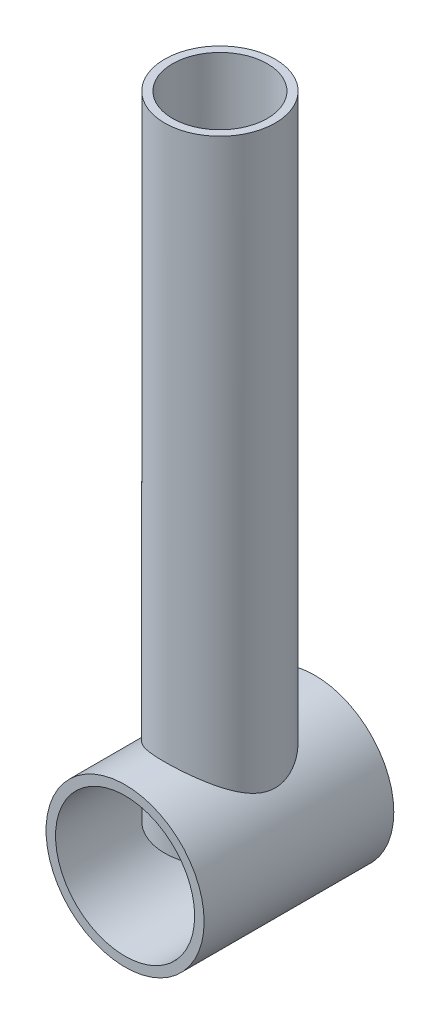
SolidWorks part; units mm, degrees
ref_plane "Ön Düzlem" through (0, 0, 0) normal (0, 0, 1) x (1, 0, 0)
ref_plane "Üst Düzlem" through (0, 0, 0) normal (0, 1, 0) x (1, 0, 0)
ref_plane "Sağ Düzlem" through (0, 0, 0) normal (1, 0, 0) x (0, 0, -1)
sketch "Çizim1" plane through (0, 0, 0) normal (0, 1, 0) x (1, 0, 0)
  circle A0 centre (0, 0) radius 17.5
  circle A1 centre (0, 0) radius 15
  dimension "D1" = 35
  dimension "D2" = 2.5
extrude "Yükseklik-Ekstrüzyon1" add sketch "Çizim1" along normal blind 200
ref_plane "Düzlem1" through (0, 0, 0) normal (0, 0, 1) x (1, 0, 0)
sketch "Çizim2" plane through (0, 0, 0) normal (0, 0, 1) x (1, 0, 0)
  line L0 (-17.5, 0) -> (17.5, 0) construction
  circle A0 centre (0, 0) radius 25
  circle A1 centre (0, 0) radius 22
extrude "Yükseklik-Ekstrüzyon2" add sketch "Çizim2" along normal blind 30 and the other way blind 30
